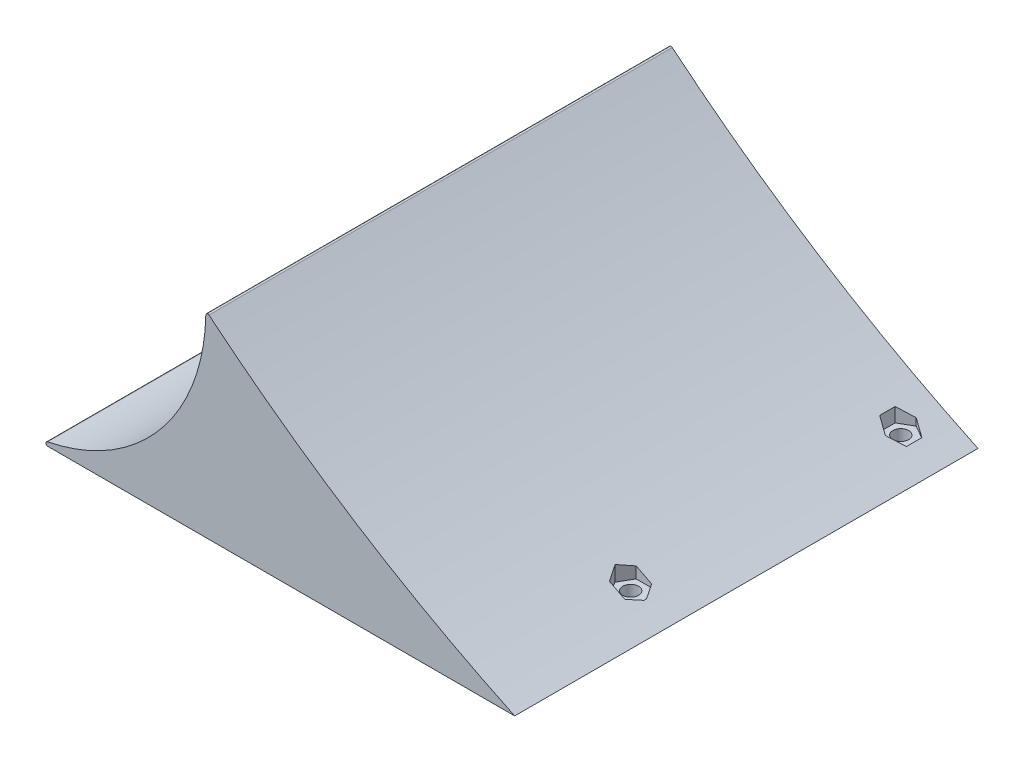
SolidWorks part; units mm, degrees
ref_plane "前视基准面" through (0, 0, 0) normal (0, 0, 1) x (1, 0, 0)
ref_plane "上视基准面" through (0, 0, 0) normal (0, 1, 0) x (1, 0, 0)
ref_plane "右视基准面" through (0, 0, 0) normal (1, 0, 0) x (0, 0, -1)
sketch "草图2" plane through (0, 0, 0) normal (0, 0, 1) x (1, 0, 0)
  circle A1 centre (0, 0) radius 33.5
  dimension "D3" = 67
sketch "草图3" plane through (0, 0, 0) normal (0, 0, 1) x (1, 0, 0)
  line L0 (0, 0) -> (0, -51) construction
  line L1 (0, -51) -> (131, -51) construction
  line L2 (131, -51) -> (0, -51)
  arc A0 (51, 0) -> (131, -51) centre (291.4441, 288.9221) ccw
  circle A1 centre (0, 0) radius 33.5 construction
  circle A2 centre (0, 0) radius 34.5
  arc A3 (0, -51) -> (51, 0) centre (0, 0) ccw
  dimension "D3" = 1
  dimension "D4" = 51
  dimension "D2" = 131
extrude "凸台-拉伸1" add sketch "草图3" along normal mid plane 240 contours A3 L2 A0 A2 region at (67.8421, -35.8914, 0)
fillet "圆角1" radius 0.5 2 edges at (0, -51, 0) (51, 0, 0)
sketch "草图4" plane through (0, 0, 0) normal (0, 1, 0) x (1, 0, 0)
  line L0 (51.8079, -120) -> (131, -120) construction
  line L1 (124.4641, -112) -> (124.4641, -108)
  line L2 (124.4641, -108) -> (121, -106)
  line L3 (121, -106) -> (117.5359, -108)
  line L4 (117.5359, -108) -> (117.5359, -112)
  line L5 (117.5359, -112) -> (121, -114)
  line L6 (121, -114) -> (124.4641, -112)
  line L7 (29.5995, -106) -> (26.1354, -108)
  line L8 (26.1354, -108) -> (26.1354, -112)
  line L9 (26.1354, -112) -> (29.5995, -114)
  line L10 (29.5995, -114) -> (33.0636, -112)
  line L11 (33.0636, -112) -> (33.0636, -108)
  line L12 (33.0636, -108) -> (29.5995, -106)
  line L13 (131, -120) -> (131, 120) construction
  line L14 (10.0015, -120) -> (50.9893, -120) construction
  line L15 (121, -110) -> (121, 110) construction
  line L16 (9.5995, 120) -> (9.5995, -120) construction
  line L17 (0, 0) -> (131, 0) construction
  line L18 (-33.5, 0) -> (33.5, 0) construction
  line L19 (33.0636, 108) -> (29.5995, 106)
  line L20 (33.0636, 112) -> (33.0636, 108)
  line L21 (29.5995, 114) -> (33.0636, 112)
  line L22 (26.1354, 112) -> (29.5995, 114)
  line L23 (26.1354, 108) -> (26.1354, 112)
  line L24 (29.5995, 106) -> (26.1354, 108)
  line L25 (121, 114) -> (124.4641, 112)
  line L26 (117.5359, 112) -> (121, 114)
  line L27 (117.5359, 108) -> (117.5359, 112)
  line L28 (121, 106) -> (117.5359, 108)
  line L29 (124.4641, 108) -> (121, 106)
  line L30 (124.4641, 112) -> (124.4641, 108)
  line L31 (29.5995, -110) -> (121, -110) construction
  line L32 (123, -36.5359) -> (119, -36.5359)
  line L33 (119, -36.5359) -> (117, -40)
  line L34 (117, -40) -> (119, -43.4641)
  line L35 (119, -43.4641) -> (123, -43.4641)
  line L36 (123, -43.4641) -> (125, -40)
  line L37 (125, -40) -> (123, -36.5359)
  line L38 (125, 40) -> (123, 43.4641)
  line L39 (123, 43.4641) -> (119, 43.4641)
  line L40 (119, 43.4641) -> (117, 40)
  line L41 (117, 40) -> (119, 36.5359)
  line L42 (119, 36.5359) -> (123, 36.5359)
  line L43 (123, 36.5359) -> (125, 40)
  line L44 (121, -110) -> (124.4641, -109.585) construction
  circle A0 centre (121, -110) radius 3.4641 construction
  circle A1 centre (29.5995, -110) radius 3.4641 construction
  circle A2 centre (29.5995, 110) radius 3.4641 construction
  circle A3 centre (121, 110) radius 3.4641 construction
  circle A4 centre (121, -40) radius 3.4641 construction
  circle A5 centre (121, 40) radius 3.4641 construction
  dimension "D1" = 4
  dimension "D2" = 10
  dimension "D3" = 10
  dimension "D4" = 10
  dimension "D5" = 20
  dimension "D6" = 80
extrude "切除-拉伸1" cut sketch "草图4" against normal offset from surface (48 mm away) 3 up to face at (70.5498, -51, 0)
sketch "草图5" plane through (0, -48, 0) normal (0, 1, 0) x (1, 0, 0)
  line L0 (33.0636, -110) -> (26.1354, -110) construction
  line L1 (33.0636, -112) -> (33.0636, -108) construction
  line L2 (26.1354, -108) -> (26.1354, -112) construction
  line L3 (31.3316, -107) -> (27.8675, -113) construction
  line L6 (33.0636, -108) -> (29.5995, -106) construction
  line L7 (29.5995, -114) -> (26.1354, -112) construction
  line L8 (26.1354, -110) -> (33.0636, -110) construction
  line L10 (75.2998, 0) -> (0, 0) construction
  line L14 (75.2998, -110) -> (33.0636, -110) construction
  line L17 (75.2998, -110) -> (75.2998, 110) construction
  line L18 (26.1354, 110) -> (124.4641, 110) construction
  line L21 (-33.5, 0) -> (33.5, 0) construction
  line L22 (26.1354, 112) -> (26.1354, 108) construction
  line L24 (124.4641, 108) -> (124.4641, 112) construction
  line L25 (118, 38.2679) -> (123.8961, 41.912) construction
  line L26 (119, 36.5359) -> (117, 40) construction
  line L27 (124.7922, 40.3598) -> (123, 43.4641) construction
  line L28 (121, -36.5359) -> (121, -43.4641) construction
  line L29 (123, -36.5359) -> (119, -36.5359) construction
  line L30 (123, -43.4641) -> (119, -43.4641) construction
  circle A0 centre (29.5995, -110) radius 2.05
  circle A2 centre (29.5995, 110) radius 2.05
  circle A6 centre (121, 110) radius 2.05
  circle A7 centre (121, -110) radius 2.05
  circle A8 centre (120.9481, 40.09) radius 2.05
  circle A9 centre (121, -40) radius 2.05
  point P17 (75.2998, 110)
  dimension "D1" = 4.1
extrude "切除-拉伸2" cut sketch "草图5" against normal blind 5 contours A0 | A8 | A2 | A7 | A9 | A6 region at (29.5995, -48, 110) region at (120.9481, -48, -40.09)
sketch "草图6" plane through (0, 0, 0) normal (0, 0, 1) x (1, 0, 0)
  line L0 (131, -51) -> (10.0995, -51) construction
  circle A0 centre (70.5498, -51) radius 70.9969
extrude "切除-拉伸3" cut sketch "草图6" along normal through all
